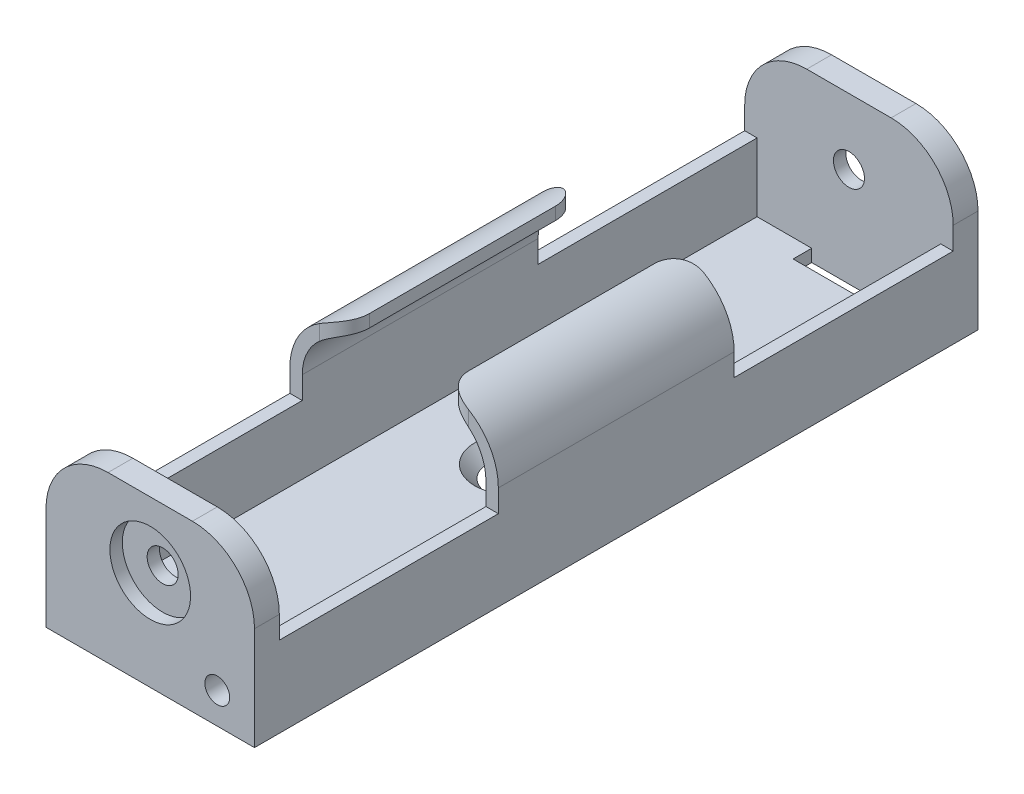
SolidWorks part; units mm, degrees
ref_plane "Спереди" through (0, 0, 0) normal (0, 0, 1) x (1, 0, 0)
ref_plane "Сверху" through (0, 0, 0) normal (0, 1, 0) x (1, 0, 0)
ref_plane "Справа" through (0, 0, 0) normal (1, 0, 0) x (0, 0, -1)
sketch "Эскиз1" plane through (0, 0, 0) normal (0, 0, 1) x (1, 0, 0)
  line L1 (-3.4, 9.15) -> (3.4, 9.15)
  line L2 (-8.4, 4.15) -> (-8.4, -4.15)
  line L3 (-8.4, -4.15) -> (8.4, -4.15)
  line L4 (8.4, 4.15) -> (8.4, -4.15)
  line L5 (0, -4.15) -> (0, 9.15) construction
  line L6 (-8.4, 0) -> (8.4, 0) construction
  arc A0 (3.4, 9.15) -> (8.4, 4.15) centre (3.4, 4.15) cw
  arc A1 (-3.4, 9.15) -> (-8.4, 4.15) centre (-3.4, 4.15) ccw
  point P0 (0, 0)
  point P6 (8.4, 9.15)
  point P10 (-8.4, 9.15)
  dimension "D3" = 5
  dimension "D1" = 13.3
  dimension "D2" = 16.8
extrude "Бобышка-Вытянуть1" add sketch "Эскиз1" along normal blind 58.3
sketch "Эскиз2" plane through (0, 9.15, 0) normal (0, 1, 0) x (1, 0, 0)
  line L1 (8.4, -19.65) -> (8.4, -2)
  line L2 (-8.4, -58.3) -> (-8.4, 0) construction
  line L8 (-8.4, -29.15) -> (8.4, -29.15) construction
  line L9 (0, -56.3) -> (0, -2) construction
  line L11 (8.4, -58.3) -> (8.4, 0) construction
  line L17 (8.4, -2) -> (-8.4, -2)
  line L18 (0, -29.15) -> (0, -56.3) construction
  line L21 (4, -36.65) -> (4, -21.65)
  line L22 (6, -19.65) -> (8.4, -19.65)
  line L24 (8.4, 0) -> (3.4, 0) construction
  line L25 (-6, -19.65) -> (-8.4, -19.65)
  line L26 (-4, -36.65) -> (-4, -21.65)
  line L28 (-8.4, -19.65) -> (-8.4, -2)
  line L29 (-8.4, -38.65) -> (-8.4, -56.3)
  line L30 (-6, -38.65) -> (-8.4, -38.65)
  line L31 (6, -38.65) -> (8.4, -38.65)
  line L32 (8.4, -56.3) -> (-8.4, -56.3)
  line L33 (8.4, -38.65) -> (8.4, -56.3)
  arc A0 (4, -21.65) -> (6, -19.65) centre (6, -21.65) cw
  arc A1 (-4, -21.65) -> (-6, -19.65) centre (-6, -21.65) ccw
  arc A2 (-4, -36.65) -> (-6, -38.65) centre (-6, -36.65) cw
  arc A3 (4, -36.65) -> (6, -38.65) centre (6, -36.65) ccw
  dimension "D4" = 2
  dimension "D1" = 2
  dimension "D2" = 4.4
  dimension "D3" = 9.5
extrude "Вырез-Вытянуть1" cut sketch "Эскиз2" against normal blind 6.8
sketch "Эскиз3" plane through (0, 0, 56.3) normal (0, 0, -1) x (-1, 0, 0)
  line L4 (-7.4, 4.15) -> (-7.4, -3.15)
  line L5 (-7.4, -3.15) -> (7.4, -3.15)
  line L6 (7.4, -3.15) -> (7.4, 4.15)
  line L7 (3.4, 8.15) -> (-3.4, 8.15)
  line L12 (-8.4, 4.15) -> (-8.4, -4.15)
  line L13 (3.4, 9.15) -> (-3.4, 9.15)
  line L14 (8.4, -4.15) -> (8.4, 4.15)
  line L15 (-8.4, -4.15) -> (8.4, -4.15)
  line L16 (-8.4, 4.15) -> (-8.4, -4.15) construction
  line L17 (3.4, 9.15) -> (-3.4, 9.15) construction
  line L18 (8.4, -4.15) -> (8.4, 4.15) construction
  line L19 (-8.4, -4.15) -> (8.4, -4.15) construction
  arc A2 (7.4, 4.15) -> (3.4, 8.15) centre (3.4, 4.15) ccw
  arc A3 (-3.4, 8.15) -> (-7.4, 4.15) centre (-3.4, 4.15) ccw
  arc A6 (-3.4, 9.15) -> (-8.4, 4.15) centre (-3.4, 4.15) ccw
  arc A7 (8.4, 4.15) -> (3.4, 9.15) centre (3.4, 4.15) ccw
  arc A8 (-3.4, 9.15) -> (-8.4, 4.15) centre (-3.4, 4.15) ccw construction
  arc A9 (8.4, 4.15) -> (3.4, 9.15) centre (3.4, 4.15) ccw construction
  dimension "D1" = 0
  dimension "D2" = 1
extrude "Вырез-Вытянуть2" cut sketch "Эскиз3" along normal blind 54.3
sketch "Эскиз5" plane through (0, -3.15, 0) normal (0, 1, 0) x (1, 0, 0)
  line L0 (8.4, -38.65) -> (8.4, -19.65) construction
  circle A1 centre (0, -29.15) radius 2
  point P8 (8.4, -29.15)
  dimension "D1" = 4
extrude "Вырез-Вытянуть4" cut sketch "Эскиз5" against normal blind 55
chamfer "Фаска2" distance 1 angle 45 1 edges at (0, -3.15, 31.15)
sketch "Эскиз7" plane through (0, 0, 0) normal (0, 0, -1) x (-1, 0, 0)
  line L0 (8.4, -4.15) -> (-8.4, -4.15) construction
  circle A0 centre (0, 3.85) radius 3.25
  dimension "D2" = 6.5
  dimension "D1" = 8
extrude "Вырез-Вытянуть5" cut sketch "Эскиз7" against normal blind 1
sketch "Эскиз8" plane through (0, 0, 0) normal (0, 0, -1) x (-1, 0, 0)
  circle A0 centre (0, 3.85) radius 3.25 construction
  circle A1 centre (0, 3.85) radius 3.25 construction
  circle A2 centre (0, 3.85) radius 1.25
  dimension "D1" = 2.5
extrude "Вырез-Вытянуть6" cut sketch "Эскиз8" against normal blind 10
sketch "Эскиз9" plane through (0, 0, 0) normal (0, 0, -1) x (-1, 0, 0)
  line L0 (8.4, -4.15) -> (-8.4, -4.15) construction
  line L1 (-8.4, -4.15) -> (-8.4, 4.15) construction
  circle A0 centre (-5.4, -1.65) radius 1
  dimension "D1" = 2
  dimension "D2" = 2.5
  dimension "D3" = 3
extrude "Вырез-Вытянуть7" cut sketch "Эскиз9" against normal blind 10
sketch "Эскиз11" plane through (0, -3.15, 0) normal (0, 1, 0) x (1, 0, 0)
  line L0 (7.4, -2) -> (-7.4, -2) construction
  line L1 (-3, -2) -> (3, -2)
  line L2 (-3, -2) -> (-3, -3.5)
  line L3 (-3, -3.5) -> (3, -3.5)
  line L4 (3, -2) -> (3, -3.5)
  line L5 (0, -3.5) -> (0, -2) construction
  line L6 (-3, -2.75) -> (3, -2.75) construction
  point P7 (0, -2)
  point P76 (0, -2.75)
  dimension "D1" = 1.5
  dimension "D2" = 6
extrude "Вырез-Вытянуть8" cut sketch "Эскиз11" against normal blind 10
ref_plane "Плоскость1" through (0, 0, 29.15) normal (0, 0, -1) x (-1, 0, 0)
mirror "Зеркальное отражение1" about plane through (0, 0, 29.15) normal (0, 0, -1) of "Вырез-Вытянуть8", "Вырез-Вытянуть5", "Вырез-Вытянуть6", "Вырез-Вытянуть7"
